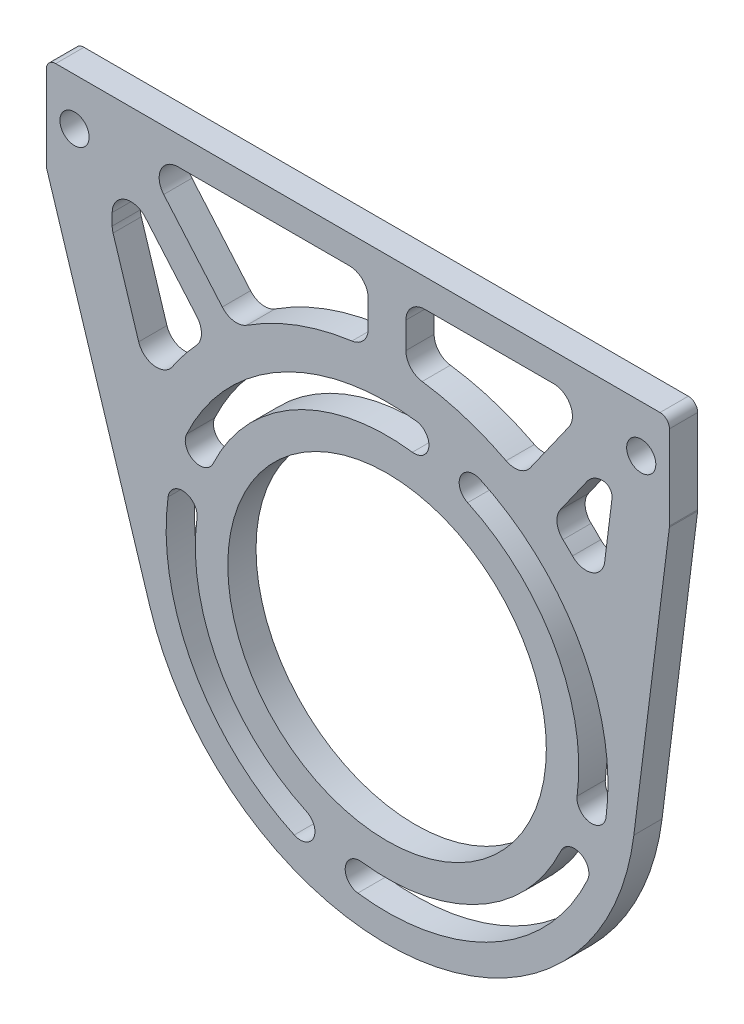
SolidWorks part; units mm, degrees
material "Thornel Mat VMA"
ref_plane "前视基准面" through (0, 0, 0) normal (0, 0, 1) x (1, 0, 0)
ref_plane "上视基准面" through (0, 0, 0) normal (0, 1, 0) x (1, 0, 0)
ref_plane "右视基准面" through (0, 0, 0) normal (1, 0, 0) x (0, 0, -1)
sketch "草图1" plane through (0, 0, 0) normal (0, 0, 1) x (1, 0, 0)
  line L0 (0, 0) -> (0, 50000) construction
  line L1 (-36.2, 37) -> (30, 37)
  line L2 (-36.2, 37) -> (-36.2, 27)
  line L3 (-36.2, 27) -> (-25.2003, -7.9347)
  line L4 (30, 37) -> (30, 27)
  line L5 (30, 27) -> (26.216, -3.2765)
  circle A0 centre (0, 0) radius 21.92 construction
  circle A1 centre (0, 0) radius 16.92
  circle A2 centre (0, 0) radius 26.42
  circle A3 centre (-33.2, 32) radius 1.55
  circle A4 centre (27, 32) radius 1.55
  arc A5 (2.6934, 20.1912) -> (3.1033, 23.2639) centre (2.8983, 21.7275) ccw
  arc A6 (-21.2972, 9.8625) -> (-18.4842, 8.5598) centre (-19.8907, 9.2112) ccw
  arc A9 (2.6934, 20.1912) -> (-18.4842, 8.5598) centre (0, 0) ccw
  arc A10 (3.1033, 23.2639) -> (-21.2972, 9.8625) centre (0, 0) ccw
  arc A11 (20.1912, -2.6934) -> (23.2639, -3.1033) centre (21.7275, -2.8983) ccw
  arc A12 (9.8625, 21.2972) -> (8.5598, 18.4842) centre (9.2112, 19.8907) ccw
  arc A13 (20.1912, -2.6934) -> (8.5598, 18.4842) centre (0, 0) ccw
  arc A14 (23.2639, -3.1033) -> (9.8625, 21.2972) centre (0, 0) ccw
  arc A15 (-2.6934, -20.1912) -> (-3.1033, -23.2639) centre (-2.8983, -21.7275) ccw
  arc A16 (21.2972, -9.8625) -> (18.4842, -8.5598) centre (19.8907, -9.2112) ccw
  arc A17 (-2.6934, -20.1912) -> (18.4842, -8.5598) centre (0, 0) ccw
  arc A18 (-3.1033, -23.2639) -> (21.2972, -9.8625) centre (0, 0) ccw
  arc A19 (-20.1912, 2.6934) -> (-23.2639, 3.1033) centre (-21.7275, 2.8983) ccw
  arc A20 (-9.8625, -21.2972) -> (-8.5598, -18.4842) centre (-9.2112, -19.8907) ccw
  arc A21 (-20.1912, 2.6934) -> (-8.5598, -18.4842) centre (0, 0) ccw
  arc A22 (-23.2639, 3.1033) -> (-9.8625, -21.2972) centre (0, 0) ccw
  point P44 (0, 0)
  dimension "D1" = 43.84
  dimension "D5" = 3.1
  dimension "D6" = 5
  dimension "D14" = 23.47
  dimension "D15" = 20.37
  dimension "D2" = 32
  dimension "D3" = 33.2
  dimension "D4" = 27
  dimension "4.5" = 4.5
  dimension "D8" = 3
  dimension "D9" = 5
  dimension "D10" = 3
  dimension "D11" = 5
  dimension "D12" = 5
  dimension "D13" = 26
  dimension "D16" = 4
extrude "凸台-拉伸1" add sketch "草图1" along normal blind 3 contours A2 L5 L4 L1 L2 L3 A4 A3 | A2 A22 A19 A21 A20 A18 A15 A17 A16 A14 A11 A13 A12 A10 A5 A9 A6 A1 region at (-4.3329, 26.3178, 0) region at (-3.9004, 25.3747, 0)
sketch "草图2" plane through (0, 0, 3) normal (0, 0, 1) x (1, 0, 0)
  line L0 (-29.2, 34) -> (-29.2, 24.7463)
  line L1 (-29.2, 24.7463) -> (-24.9957, 11.3936)
  line L2 (-29.2, 34) -> (-2, 34)
  line L3 (-2, 34) -> (-2, 27.3971)
  line L4 (2, 27.3971) -> (2, 34)
  line L5 (2, 34) -> (24, 34)
  line L6 (24, 34) -> (24, 27.3735)
  line L7 (24, 27.3735) -> (22.5411, 15.7003)
  line L8 (30, 27) -> (26.216, -3.2765) construction
  line L9 (-36.2, 27) -> (-25.2003, -7.9347) construction
  line L10 (-36.2, 37) -> (30, 37) construction
  line L11 (0, 0) -> (0, 50000) construction
  line L12 (-29.2, 31.6977) -> (-19.0087, 19.8311)
  line L13 (-26.5637, 34) -> (-16.3327, 22.0872)
  line L14 (21.5519, 34) -> (14.1655, 23.5359)
  line L15 (17.3641, 21.2859) -> (24, 30.6867)
  line L16 (-29.2, 34) -> (0, 0) construction
  line L17 (0, 0) -> (24, 34) construction
  circle A0 centre (0, 0) radius 27.47
  arc A1 (23.2639, -3.1033) -> (9.8625, 21.2972) centre (0, 0) ccw construction
  circle A2 centre (-33.2, 32) radius 1.55 construction
  circle A4 centre (27, 32) radius 1.55 construction
  dimension "D1" = 4
  dimension "D5" = 4
  dimension "D2" = 3
  dimension "D3" = 4
  dimension "D4" = 2
  dimension "D6" = 6
  dimension "D7" = 3
  dimension "D8" = 6
  dimension "D9" = 1.5
  dimension "D10" = 2
  dimension "D11" = 2
extrude "切除-拉伸1" cut sketch "草图2" against normal blind 3 contours A0 L3 L2 L0 L1 | A0 L7 L6 L5 L4 | A0 L12 L0 L1 | A0 L7 L6 L15 region at (-25.0394, 21.4395, 3) region at (-13.1862, 29.7551, 3) region at (10.8558, 30.0865, 3) region at (21.4624, 22.7917, 3)
fillet "圆角2" radius 2 15 edges at (-24.9957, 11.3936, 1.5) (-29.2, 31.6977, 1.5) (-19.0087, 19.8311, 1.5) (-29.2, 24.7463, 1.5) (24, 30.6867, 1.5) (22.5411, 15.7003, 1.5) (17.3641, 21.2859, 1.5) (2, 27.3971, 1.5) (21.5519, 34, 1.5) (14.1655, 23.5359, 1.5) (2, 34, 1.5) (-16.3327, 22.0872, 1.5) (-26.5637, 34, 1.5) (-2, 27.3971, 1.5) (-2, 34, 1.5)
fillet "圆角3" radius 1 1 edges at (24, 27.3735, 1.5)
fillet "圆角4" radius 1 4 edges at (-36.2, 27, 1.5) (30, 37, 1.5) (30, 27, 1.5) (-36.2, 37, 1.5)
